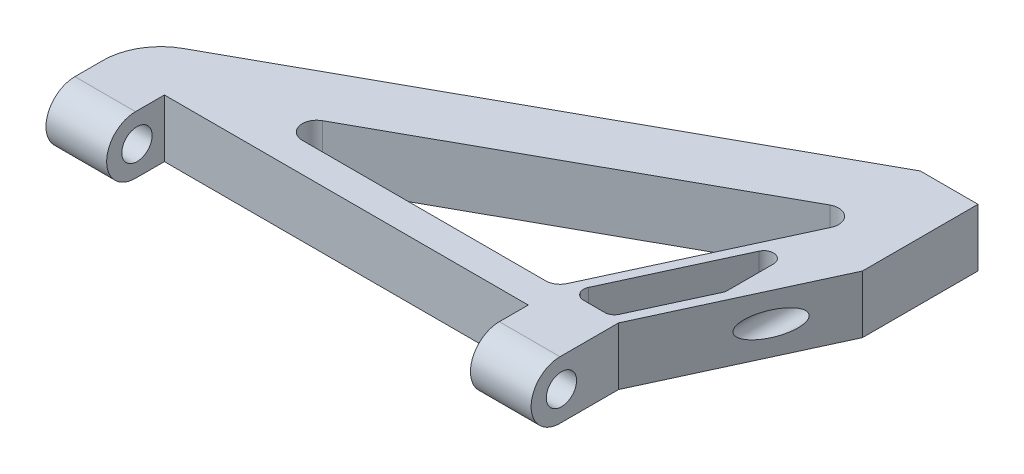
SolidWorks part; units mm, degrees
other "Markup1"
sketch "Sketch9" plane through (-9.525, 19.05, 0) normal (-0.761, 0.4779, -0.4388) x (-0.0596, 0.622, 0.7808)
material "6061-T6 (SS)"
ref_plane "Front Plane" through (0, 0, 0) normal (0, 0, 1) x (1, 0, 0)
ref_plane "Top Plane" through (0, 0, 0) normal (0, 1, 0) x (1, 0, 0)
ref_plane "Right Plane" through (0, 0, 0) normal (1, 0, 0) x (0, 0, -1)
sketch "Sketch1" plane through (0, 0, 0) normal (0, 1, 0) x (1, 0, 0)
  line L0 (0, 0) -> (0, -122) construction
  line L1 (0, 0) -> (165.875, 0) construction
  line L2 (165.875, 0) -> (165.875, -38.1) construction
  line L3 (156.35, 0) -> (175.4, 0)
  line L4 (175.4, 0) -> (175.4, -38.1)
  line L5 (0, -122) -> (0, -112) construction
  line L7 (10, -122) -> (-10, -122)
  line L12 (10, -102.95) -> (10, -122)
  line L13 (-76.2946, -112) -> (175.6699, -112) construction
  line L14 (140, -122) -> (-10, -122) construction
  line L15 (150, -122) -> (130, -122)
  line L16 (130, -122) -> (130, -102.95)
  line L17 (150, -122) -> (150, -93.1649)
  line L20 (150, -93.1649) -> (175.4, -38.1)
  line L21 (10, -102.95) -> (130, -102.95)
  line L24 (130, -102.95) -> (130, -54.7662) construction
  line L27 (157.7866, -30.8036) -> (130.2977, -90.3973)
  line L28 (151.1571, -24.6412) -> (43.4028, -84.2348)
  line L29 (45.7076, -93.1649) -> (125.9731, -93.1649)
  line L31 (-10, -92) -> (156.35, 0)
  line L32 (-10, -122) -> (-10, -92)
  line L34 (165.875, 0) -> (165.875, 30) construction
  arc A7 (45.7076, -93.1649) -> (43.4028, -84.2348) centre (45.7076, -88.4024) cw
  arc A8 (125.9731, -93.1649) -> (130.2977, -90.3973) centre (125.9731, -88.4024) ccw
  arc A9 (151.1571, -24.6412) -> (157.7866, -30.8036) centre (153.462, -28.8088) cw
  point P7 (165.875, 0)
  point P11 (70, -96.6)
  point P13 (0, -112)
  point P16 (0, -122)
  point P20 (140, -122)
  point P28 (129.021, -93.1649)
  point P36 (165.875, -35.3491)
  point P45 (162.8454, -13.5799)
  point P48 (22.05, -96.6)
  dimension "D12" = 30
  dimension "D13" = 19.05
  dimension "D14" = 19.05
  dimension "D18" = 4.7625
  dimension "D15" = 4.7625
  dimension "D2" = 15.875
  dimension "D3" = 38.1
  dimension "D4" = 38.1
  dimension "D5" = 112
  dimension "D6" = 20
  dimension "D7" = 140
  dimension "D8" = 20
  dimension "D9" = 10
  dimension "D10" = 19.05
  dimension "D11" = 19.05
  dimension "D16" = 30
extrude "Boss-Extrude1" add sketch "Sketch1" along normal blind 19.05 contours L12 L21 L16 L15 L17 L20 L4 L3 L7 region at (165.875, 0, 2.2194)
sketch "Sketch3" plane through (0, 0, 0) normal (0, 0, -1) x (-1, 0, 0)
  line L0 (-156.35, 19.05) -> (-175.4, 19.05) construction
  line L1 (-175.4, 19.05) -> (-175.4, 0) construction
  circle A0 centre (-165.875, 9.525) radius 3.9687
  dimension "D1" = 7.9375
  dimension "D3" = 9.525
  dimension "D2" = 9.525
extrude "Cut-Extrude1" cut sketch "Sketch3" against normal up to next
fillet "Fillet1" 2 edges at (0, 19.05, 122) (0, 0, 122) type full round first side face at (97.0136, 19.05, 83.3786) second side face at (97.0136, 0, 83.3786) middle face at (0, 9.525, 122)
sketch "Sketch6" plane through (150, 0, 0) normal (1, 0, 0) x (0, 0, -1)
  line L1 (-112, 0) -> (-112, 19.05) construction
  line L2 (-122, 19.05) -> (-93.1649, 19.05) construction
  circle A0 centre (-112, 9.525) radius 5
  point P4 (-112, 9.525)
  point P5 (-112, 0)
  dimension "D1" = 10
extrude "Cut-Extrude3" cut sketch "Sketch6" against normal through all
fillet "Fillet2" 2 edges at (140, 19.05, 122) (140, 0, 122) type full round first side face at (97.0136, 19.05, 81.6468) second side face at (97.0136, 0, 81.6468) middle face at (140, 9.525, 122)
fillet "Fillet6" radius 19.05 1 edges at (-10, 9.525, 92)
sketch "Sketch8" [suppressed] plane through (0, 19.05, 0) normal (0, 1, 0) x (1, 0, 0)
  line L4 (124.165, -36.1434) -> (43.4987, -83.1988) construction
  line L10 (160.5971, -158.3087) -> (103.1838, -57.8355)
  line L11 (130.8738, -89.8648) -> (115.3014, -62.613)
  line L12 (160.1788, -156.7334) -> (160.1788, 27.2514)
  line L13 (126.0432, -94.615) -> (128.1172, -94.615)
  line L14 (136.525, -92.075) -> (161.192, -5.7404) construction
  line L15 (81.7133, -27.9414) -> (112.9323, -82.5745) construction
  line L16 (156.3688, -22.6219) -> (156.3688, 0) construction
  line L17 (9.525, -98.425) -> (117.475, -98.425) construction
  line L18 (108.2246, -66.6568) -> (123.2866, -93.0152)
  line L19 (109.406, -62.3249) -> (110.9695, -61.4315)
  line L20 (107.5158, -59.0169) -> (147.6154, -36.1028)
  line L21 (149.093, -34.2184) -> (166.4066, 26.3792)
  line L34 (144.6213, -12.095) -> (144.6213, -17.9761)
  line L35 (122.2453, -32.8524) -> (41.579, -79.9078)
  line L36 (143.046, -20.7186) -> (113.4191, -38.001)
  line L37 (148.4313, 0) -> (148.4313, -50.4031) construction
  line L38 (98.8839, -33.2473) -> (3.8265, -88.6975)
  line L39 (109.0769, -36.8583) -> (106.5172, -32.4703)
  line L40 (105.7859, -38.778) -> (103.2262, -34.39)
  line L41 (104.6431, -43.1203) -> (17.108, -94.1825)
  line L45 (137.6708, -10.6216) -> (1.846, -89.8528)
  line L46 (-5.715, -103.0168) -> (-5.715, -104.14)
  line L47 (-5.715, -104.14) -> (5.715, -104.14)
  line L48 (5.715, -104.14) -> (5.715, -94.615)
  line L49 (5.715, -94.615) -> (121.285, -94.615)
  line L50 (121.285, -94.615) -> (121.285, -104.14)
  line L51 (121.285, -104.14) -> (132.715, -104.14)
  line L52 (132.715, -104.14) -> (132.715, -91.5414)
  line L53 (132.715, -91.5414) -> (157.5286, -4.6937)
  line L55 (157.7528, -3.81) -> (145.0012, -3.81)
  line L57 (139.8465, -9.3525) -> (107.6599, -28.128)
  line L61 (5.4262, -94.615) -> (15.5082, -94.615)
  line L65 (132.715, -91.5414) -> (157.5286, -4.6937)
  arc A6 (123.2866, -93.0152) -> (126.0432, -94.615) centre (126.0432, -91.44) ccw
  arc A7 (130.8738, -89.8648) -> (128.1172, -94.615) centre (128.1172, -91.44) cw
  arc A8 (110.9695, -61.4315) -> (115.3014, -62.613) centre (112.5447, -64.1882) cw
  arc A9 (109.406, -62.3249) -> (108.2246, -66.6568) centre (110.9813, -65.0816) ccw
  arc A10 (107.5158, -59.0169) -> (103.1838, -57.8355) centre (105.9405, -56.2603) cw
  arc A11 (147.6154, -36.1028) -> (149.093, -34.2184) centre (146.0402, -33.3462) ccw
  arc A12 (160.5971, -158.3087) -> (160.1788, -156.7334) centre (163.3538, -156.7334) cw
  arc A13 (160.1788, 27.2514) -> (166.4066, 26.3792) centre (163.3538, 27.2514) cw
  arc A14 (144.6213, -12.095) -> (139.8465, -9.3525) centre (141.4462, -12.095) ccw
  arc A15 (17.108, -94.1825) -> (15.5082, -94.615) centre (15.5082, -91.44) cw
  arc A16 (3.8265, -88.6975) -> (5.4262, -94.615) centre (5.4262, -91.44) ccw
  arc A17 (105.7859, -38.778) -> (104.6431, -43.1203) centre (103.0434, -40.3778) cw
  arc A18 (103.2262, -34.39) -> (98.8839, -33.2473) centre (100.4837, -35.9898) ccw
  arc A19 (106.5172, -32.4703) -> (107.6599, -28.128) centre (109.2597, -30.8705) cw
  arc A20 (109.0769, -36.8583) -> (113.4191, -38.001) centre (111.8194, -35.2585) ccw
  arc A21 (144.6213, -17.9761) -> (143.046, -20.7186) centre (141.4462, -17.9761) cw
  arc A26 (1.846, -89.8528) -> (-5.715, -103.0168) centre (9.525, -103.0168) ccw
  arc A28 (157.5286, -4.6937) -> (157.7528, -3.81) centre (142.875, -0.507) ccw
  arc A29 (137.6708, -10.6216) -> (145.0012, -3.81) centre (126.1523, 9.1243) ccw
  dimension "D4" = 3.81
  dimension "D5" = 3.175
  dimension "D3" = 3.81
  dimension "D6" = 3.175
  dimension "D7" = 3.81
  dimension "D10" = 3.175
  dimension "D2" = 3.81
  dimension "D8" = 3.81
  dimension "D9" = 3.81
  dimension "D11" = 3.81
  dimension "D12" = 3.81
  dimension "D13" = 3.81
  dimension "D15" = 43.18
  dimension "D16" = 48.7737
extrude "Cut-Extrude4" [suppressed] cut sketch "Sketch8" against normal blind 12.7 contours A21 L34 A14 L57 A19 L39 A20 L36 | L40 A18 L38 A16 L61 A15 L41 A17 | A13 L12 A12 L10 A10 L20 A11 L21 | L19 A9 L18 A6 L13 A7 L11 A8
thread "Thread2" pitch 1.0583 method cut profile "Thread Profile2" start angle 0, offset 0, length 28.575, pitch 1.0583, diameter 7.9375
ref_plane "Plane2" through (169.8437, 9.525, 0) normal (0, -1, 0) x (1, 0, 0)
sketch "Thread Profile2" plane through (169.8437, 9.525, 0) normal (0, -1, 0) x (1, 0, 0)
  line L0 (0, 0) -> (0, 1.0583) construction
  line L1 (0, 0) -> (0.5728, 0.3307)
  line L2 (0.5728, 0.3307) -> (0.5728, 0.463)
  line L3 (0.5728, 0.463) -> (0, 0.7937)
  line L4 (0.5728, 0.3969) -> (0, 0.3969) construction
  line L11 (0, 0) -> (0, 0.7937)
  point P2 (0, 0)
  dimension "Pitch" = 1.0583
  dimension "Profile_Angle" = 60
  dimension "Profile_Land" = 0.1323
  dimension "Profile_Height" = 0.5728
sketch "Sketch10" plane through (0, 0, 0) normal (1, 0, 0) x (0, 0, -1)
  point P0 (-112, 9.525)
sketch3d "3DSketch2"
  line L0 (0, 9.525, 112) -> (167.6024, 9.525, 112) construction
  circle A0 centre (150, 9.525, 112) radius 5 construction
  circle A1 centre (-10, 9.525, 112) radius 5 construction
  point P5 (155, 9.525, 112)
  point P9 (-5, 9.525, 112)
sketch "Sketch11" plane through (0, 19.05, 0) normal (0, 1, 0) x (1, 0, 0)
  line L6 (144.909, -9.9557) -> (93.7646, -38.2411)
  line L36 (147.6761, -90.6228) -> (158.4393, -67.2892)
  line L39 (147.9821, -22.7689) -> (99.911, -49.3547)
  line L41 (152.6732, -49.4692) -> (134.917, -87.9631)
  line L42 (41.8662, -81.4565) -> (30.0239, -88.0058)
  line L43 (28.4873, -88.4024) -> (15.3665, -88.4024)
  line L44 (149.6205, -19.9905) -> (149.6205, -12.7341)
  line L45 (91.5758, -53.9645) -> (41.8662, -81.4565)
  line L46 (144.793, -92.468) -> (137.8, -92.468)
  line L48 (95.596, -48.1129) -> (92.5228, -42.5561)
  line L49 (158.7312, -50.7991) -> (158.7312, -65.9593)
  line L50 (92.8176, -49.6495) -> (89.7444, -44.0927)
  line L51 (85.4294, -42.8509) -> (13.8299, -82.449)
  arc A10 (132.7904, -92.468) -> (133.1807, -91.7271) centre (125.9731, -88.4024) ccw
  arc A12 (134.917, -87.9631) -> (137.8, -92.468) centre (137.8, -89.293) ccw
  arc A13 (144.793, -92.468) -> (147.6761, -90.6228) centre (144.793, -89.293) ccw
  arc A14 (158.7312, -65.9593) -> (158.4393, -67.2892) centre (155.5562, -65.9593) cw
  arc A15 (158.7312, -50.7991) -> (152.6732, -49.4692) centre (155.5562, -50.7991) ccw
  arc A16 (149.6205, -12.7341) -> (144.909, -9.9557) centre (146.4455, -12.7341) ccw
  arc A17 (147.9821, -22.7689) -> (149.6205, -19.9905) centre (146.4455, -19.9905) ccw
  arc A18 (92.5228, -42.5561) -> (93.7646, -38.2411) centre (95.3012, -41.0195) cw
  arc A19 (95.596, -48.1129) -> (99.911, -49.3547) centre (98.3744, -46.5763) ccw
  arc A20 (89.7444, -44.0927) -> (85.4294, -42.8509) centre (86.966, -45.6293) ccw
  arc A21 (92.8176, -49.6495) -> (91.5758, -53.9645) centre (90.0392, -51.1861) cw
  arc A22 (30.0239, -88.0058) -> (28.4873, -88.4024) centre (28.4873, -85.2274) cw
  arc A23 (15.3665, -88.4024) -> (13.8299, -82.449) centre (15.3665, -85.2274) cw
  dimension "D1" = 3.175
  dimension "D2" = 3.175
extrude "Cut-Extrude5" cut sketch "Sketch11" against normal offset from surface (15.875 mm away) 3.175 contours L49 A15 L41 A12 L46 A13 L36 A14 region at (148.5126, 19.05, 72.4219) up to face at (88.7255, 0, 81.2934)
sketch "Sketch12" plane through (36.6209, 0, 66.2162) normal (-0.484, 0, -0.8751) x (-0.8751, 0, 0.484)
  line L0 (2.7857, 15.875) -> (-120.35, 15.875)
  line L2 (-120.35, 3.175) -> (2.7857, 3.175)
  line L4 (-120.35, 0) -> (2.7857, 0)
  line L5 (-120.35, 19.05) -> (-120.35, 0)
  line L6 (2.7857, 19.05) -> (-120.35, 19.05)
  line L7 (2.7857, 0) -> (2.7857, 19.05)
  line L8 (-120.35, 0) -> (2.7857, 0) construction
  line L9 (-120.35, 15.875) -> (-120.35, 3.175)
  line L10 (2.7857, 19.05) -> (-120.35, 19.05) construction
  line L11 (2.7857, 3.175) -> (2.7857, 15.875)
  line L12 (-117.175, 15.875) -> (-117.175, 3.175) construction
  line L13 (-0.3893, 3.175) -> (-0.3893, 15.875) construction
  line L14 (-0.3893, 15.875) -> (-117.175, 15.875) construction
  line L15 (-117.175, 3.175) -> (-0.3893, 3.175) construction
  line L17 (-120.35, 19.05) -> (-120.35, 0) construction
  line L18 (2.7857, 0) -> (2.7857, 19.05) construction
  dimension "D1" = 0
  dimension "D2" = 3.175
move or copy body "Body-Move/Copy2" [suppressed] bodies to move or copy 105
move or copy body "Body-Move/Copy1" [suppressed] bodies to move or copy 105
